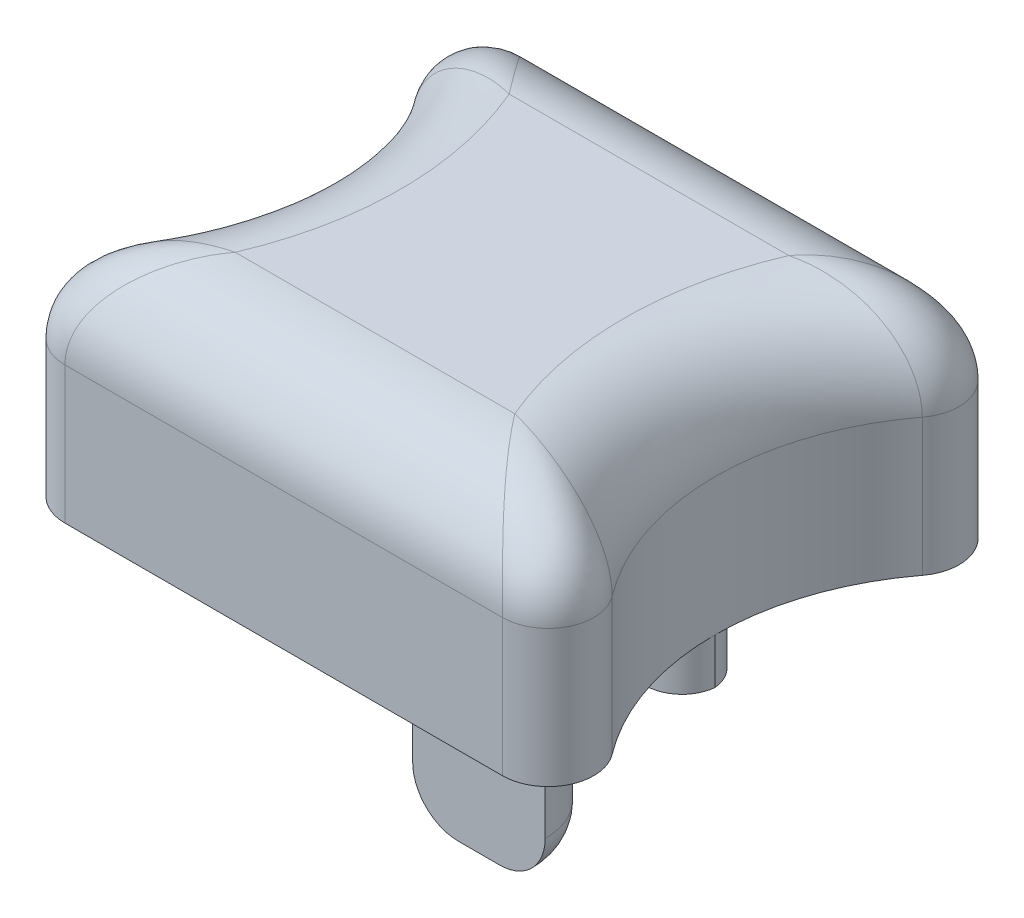
SolidWorks part; units mm, degrees
ref_plane "Front Plane" through (0, 0, 0) normal (0, 0, 1) x (1, 0, 0)
ref_plane "Top Plane" through (0, 0, 0) normal (0, 1, 0) x (1, 0, 0)
ref_plane "Right Plane" through (0, 0, 0) normal (1, 0, 0) x (0, 0, -1)
sketch "Sketch1" plane through (0, 0, 0) normal (0, 1, 0) x (1, 0, 0)
  line L0 (-1.45, 0) -> (1.45, 0)
  arc A0 (1.45, 0) -> (-1.45, 0) centre (0, 0) ccw
  dimension "D1" = 2.9
extrude "Boss-Extrude1" add sketch "Sketch1" along normal blind 5
sketch "Sketch2" plane through (0, 5, 0) normal (0, 1, 0) x (1, 0, 0)
  line L0 (-1.45, 0) -> (1.45, 0) construction
  line L1 (-4.45, 1.45) -> (4.45, 1.45)
  line L2 (-4.45, 1.45) -> (-4.45, 0)
  line L3 (-4.45, 0) -> (4.45, 0)
  line L4 (4.45, 1.45) -> (4.45, 0)
  arc A0 (1.45, 0) -> (-1.45, 0) centre (0, 0) ccw construction
  dimension "D1" = 3
  dimension "D2" = 3
extrude "Boss-Extrude2" add sketch "Sketch2" along normal blind 1
fillet "Fillet1" radius 1 1 edges at (0, 0, -1.45)
fillet "Fillet2" radius 0.8 4 edges at (-4.45, 5.5, -1.45) (-4.45, 5.5, 0) (4.45, 5.5, 0) (4.45, 5.5, -1.45)
sketch "Sketch3" plane through (0, 6, 0) normal (0, 1, 0) x (1, 0, 0)
  line L0 (-4.4465, 0.725) -> (4.4465, 0.725) construction
  line L2 (7.5, 5.725) -> (-7.5, 5.725)
  line L3 (7.5, 5.725) -> (7.5, -4.275)
  line L4 (7.5, -4.275) -> (-7.5, -4.275)
  line L5 (-7.5, 5.725) -> (-7.5, -4.275)
  line L6 (7.5, 5.725) -> (-7.5, -4.275) construction
  line L7 (7.5, -4.275) -> (-7.5, 5.725) construction
  point P4 (0, 0.725)
  dimension "D1" = 15
  dimension "D2" = 10
extrude "Boss-Extrude3" add sketch "Sketch3" along normal blind 5
sketch "Sketch5" plane through (0, 6, 0) normal (0, -1, 0) x (1, 0, 0)
  line L0 (-7.5, 4.275) -> (-7.5, -5.725)
  line L1 (0, 4.275) -> (0, -5.725) construction
  line L2 (-7.5, 4.275) -> (7.5, 4.275) construction
  line L3 (7.5, -5.725) -> (-7.5, -5.725) construction
  line L4 (7.5, 4.275) -> (7.5, -5.725)
  arc A0 (-7.5, 4.275) -> (-7.5, -5.725) centre (-10.0669, -0.725) cw
  arc A1 (7.5, 4.275) -> (7.5, -5.725) centre (10.0669, -0.725) ccw
extrude "Cut-Extrude2" cut sketch "Sketch5" against normal blind 10
fillet "Fillet7" radius 1 4 edges at (7.5, 8.5, 4.275) (-7.5, 8.5, 4.275) (-7.5, 8.5, -5.725) (7.5, 8.5, -5.725)
fillet "Fillet8" radius 2 8 edges at (-5.6871, 11, 3.7199) (-4.4465, 11, -0.725) (-5.6871, 11, -5.1699) (0, 11, -5.725) (5.6871, 11, -5.1699) (4.4465, 11, -0.725) (5.6871, 11, 3.7199) (0, 11, 4.275)
